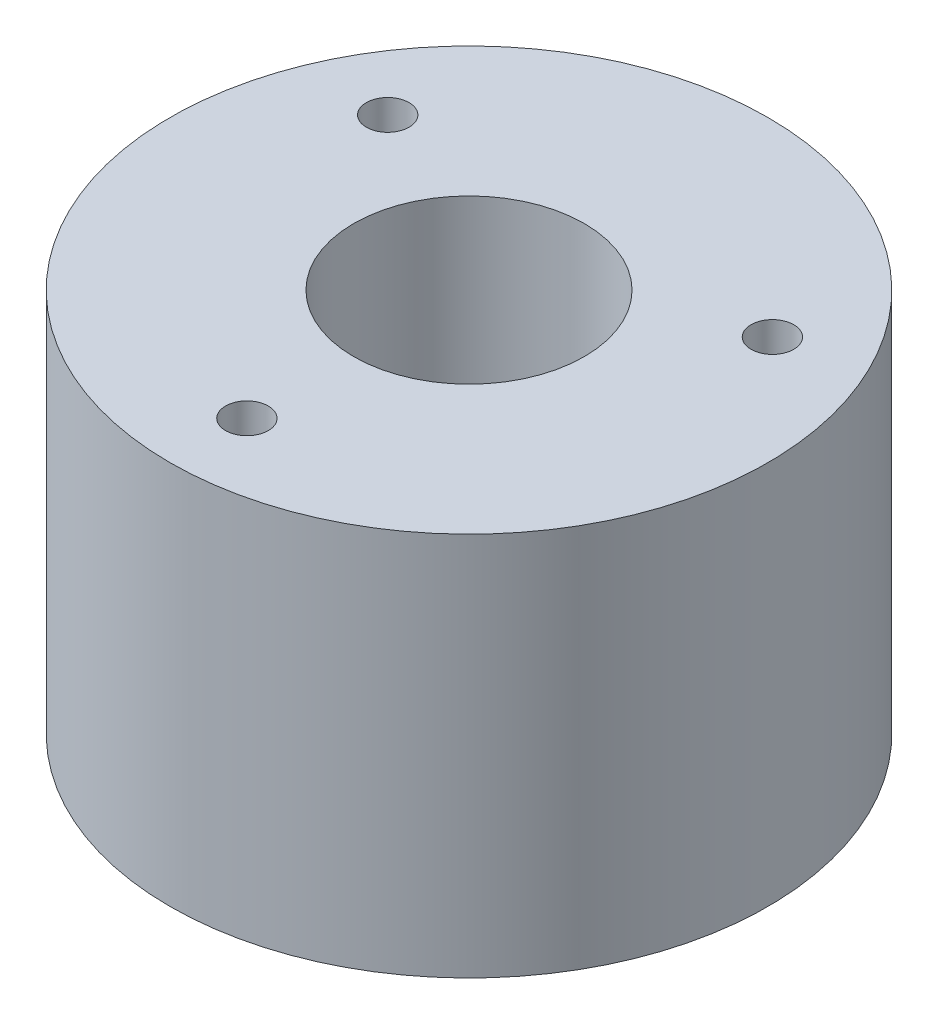
SolidWorks part; units mm, degrees
material "6061-T6 (SS)"
ref_plane "Front Plane" through (0, 0, 0) normal (0, 0, 1) x (1, 0, 0)
ref_plane "Top Plane" through (0, 0, 0) normal (0, 1, 0) x (1, 0, 0)
ref_plane "Right Plane" through (0, 0, 0) normal (1, 0, 0) x (0, 0, -1)
sketch "Sketch1" plane through (0, 0, 0) normal (0, 1, 0) x (1, 0, 0)
  circle A0 centre (0, 0) radius 22.225
  circle A1 centre (0, 0) radius 8.5725
  dimension "D1" = 44.45
  dimension "D2" = 17.145
extrude "Boss-Extrude1" add sketch "Sketch1" along normal blind 28.575
sketch "Sketch2" plane through (0, 0, 0) normal (0, -1, 0) x (1, 0, 0)
  line L1 (6.9215, 11.9884) -> (-6.9215, 11.9884)
  line L2 (-6.9215, 11.9884) -> (-13.843, 0)
  line L3 (-13.843, 0) -> (-6.9215, -11.9884)
  line L4 (-6.9215, -11.9884) -> (6.9215, -11.9884)
  line L5 (6.9215, -11.9884) -> (13.843, 0)
  line L6 (13.843, 0) -> (6.9215, 11.9884)
  circle A0 centre (0, 0) radius 11.9884 construction
  circle A1 centre (-6.9215, 11.9884) radius 1.5875
  circle A2 centre (6.9215, 11.9884) radius 1.5875
  circle A3 centre (13.843, 0) radius 1.5875
  circle A4 centre (6.9215, -11.9884) radius 1.5875
  circle A5 centre (-6.9215, -11.9884) radius 1.5875
  circle A6 centre (-13.843, 0) radius 1.5875
  point P22 (0, 0)
  circle M3 centre (0, 0) radius 8.5725
  dimension "D2" = 3.175
  dimension "D3" = 6
  dimension "D1" = 13.843
extrude "Cut-Extrude1" cut sketch "Sketch2" against normal blind 9.9219 contours L2 A6 L3 | L3 A6 L2 | A6 L3 A5 L4 A4 L5 A3 L6 A2 L1 A1 L2 M3 | L3 A5 L4 | L4 A5 L3 | L4 A4 L5 | L5 A4 L4 | L5 A3 L6 | L6 A3 L5 | L6 A2 L1 | L1 A2 L6 | L1 A1 L2 | L2 A1 L1 region at (-6.4839, 0, 11.2304) region at (-7.1403, 0, 12.3674) region at (0, 0, 11.634) region at (7.1403, 0, 12.3674) region at (6.4839, 0, 11.2304) region at (-12.9678, 0, 0) region at (-14.2806, 0, 0) region at (14.2806, 0, 0) region at (12.9678, 0, 0) region at (-6.4839, 0, -11.2304) region at (-7.1403, 0, -12.3674) region at (7.1403, 0, -12.3674) region at (6.4839, 0, -11.2304)
fillet "Fillet1" radius 3.175 12 edges at (-13.0493, 4.9609, -1.3748) (-7.7153, 4.9609, -10.6136) (-5.334, 4.9609, -11.9884) (5.334, 4.9609, -11.9884) (7.7152, 4.9609, -10.6136) (13.0492, 4.9609, -1.3748) (13.0493, 4.9609, 1.3748) (7.7153, 4.9609, 10.6136) (5.334, 4.9609, 11.9884) (-5.334, 4.9609, 11.9884) (-7.7153, 4.9609, 10.6136) (-13.0492, 4.9609, 1.3748)
sketch "Sketch3" plane through (0, 0, 0) normal (0, -1, 0) x (1, 0, 0)
  line L0 (3.3717, 11.9884) -> (-3.3717, 11.9884) construction
  circle A0 centre (0, 16.51) radius 1.5875
  circle A1 centre (14.2981, -8.255) radius 1.5875
  circle A2 centre (-14.2981, -8.255) radius 1.5875
  point P2 (0, 11.9884)
  point P7 (22.9013, -5.9445)
  point P8 (0, 0)
  point P12 (0, 0)
  dimension "D2" = 3.175
  dimension "D1" = 16.51
  dimension "D3" = 3
extrude "Cut-Extrude2" cut sketch "Sketch3" against normal through all
